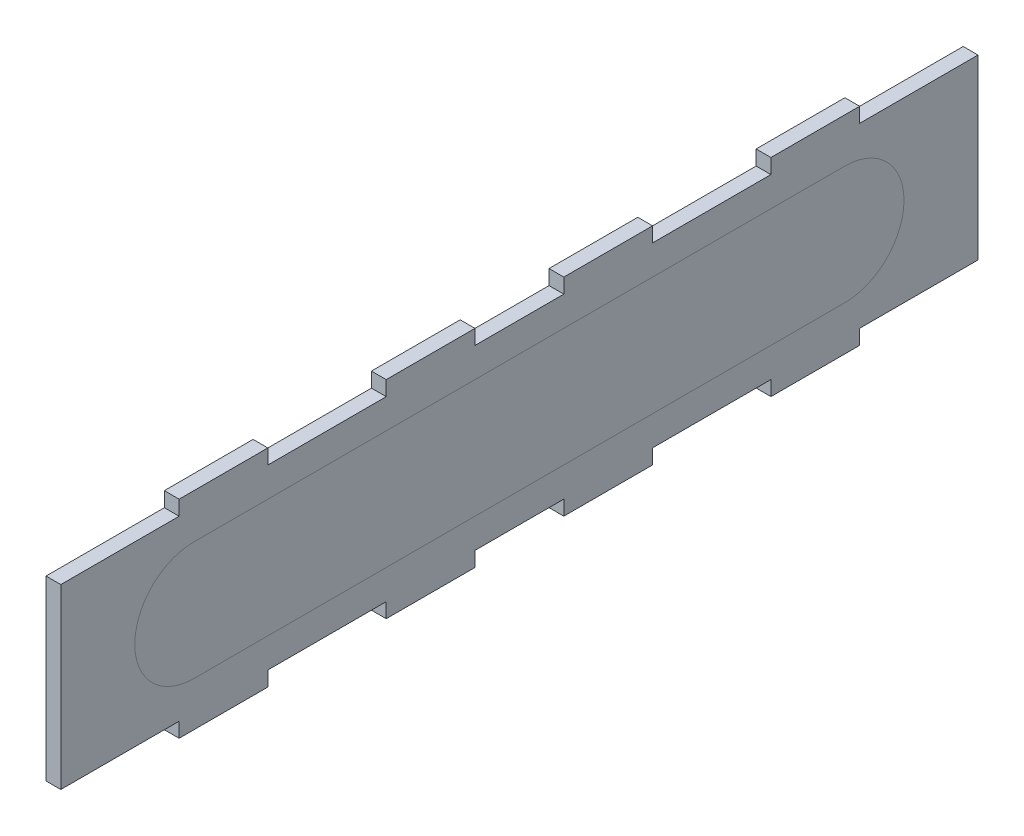
SolidWorks part; units mm, degrees
material "Maple"
ref_plane "Front Plane" through (0, 0, 0) normal (0, 0, 1) x (1, 0, 0)
ref_plane "Top Plane" through (0, 0, 0) normal (0, 1, 0) x (1, 0, 0)
ref_plane "Right Plane" through (0, 0, 0) normal (1, 0, 0) x (0, 0, -1)
sketch "Sketch1" plane through (0, 0, 0) normal (1, 0, 0) x (0, 0, -1)
  line L0 (-77.507, 17.5) -> (77.507, 17.5) construction
  line L1 (-77.507, -15) -> (77.507, -15) construction
  line L2 (-77.507, -15) -> (-77.507, 15) construction
  line L3 (-77.507, 15) -> (77.507, 15) construction
  line L4 (77.507, -15) -> (77.507, 15) construction
  line L5 (-77.507, -15) -> (77.507, 15) construction
  line L6 (-77.507, 15) -> (77.507, -15) construction
  line L7 (-77.507, -17.5) -> (77.507, -17.5) construction
  line L8 (-20.5112, 0) -> (21.2154, 0) construction
  line L9 (0, 9.427) -> (0, -9.8875) construction
  line L10 (-77.507, 15) -> (-77.507, -15)
  line L11 (-77.507, -15) -> (-57.507, -15)
  line L12 (-57.507, -15) -> (-57.507, -17.5)
  line L13 (-57.507, -17.5) -> (-42.507, -17.5)
  line L14 (-42.507, -17.5) -> (-42.507, -15)
  line L15 (-42.507, -15) -> (-22.507, -15)
  line L16 (-22.507, -15) -> (-22.507, -17.5)
  line L17 (-22.507, -17.5) -> (-7.507, -17.5)
  line L18 (-7.507, -17.5) -> (-7.507, -15)
  line L19 (-7.507, -15) -> (7.507, -15)
  line L20 (-7.507, 15) -> (7.507, 15)
  line L21 (-7.507, 17.5) -> (-7.507, 15)
  line L22 (-22.507, 17.5) -> (-7.507, 17.5)
  line L23 (-22.507, 15) -> (-22.507, 17.5)
  line L24 (-42.507, 15) -> (-22.507, 15)
  line L25 (-42.507, 17.5) -> (-42.507, 15)
  line L26 (-57.507, 17.5) -> (-42.507, 17.5)
  line L27 (-57.507, 15) -> (-57.507, 17.5)
  line L28 (-77.507, 15) -> (-57.507, 15)
  line L29 (7.507, -17.5) -> (7.507, -15)
  line L30 (22.507, -17.5) -> (7.507, -17.5)
  line L31 (22.507, -15) -> (22.507, -17.5)
  line L32 (42.507, -15) -> (22.507, -15)
  line L33 (42.507, -17.5) -> (42.507, -15)
  line L34 (57.507, -17.5) -> (42.507, -17.5)
  line L35 (57.507, -15) -> (57.507, -17.5)
  line L36 (77.507, -15) -> (57.507, -15)
  line L37 (77.507, 15) -> (77.507, -15)
  line L38 (77.507, 15) -> (57.507, 15)
  line L39 (57.507, 15) -> (57.507, 17.5)
  line L40 (57.507, 17.5) -> (42.507, 17.5)
  line L41 (42.507, 17.5) -> (42.507, 15)
  line L42 (42.507, 15) -> (22.507, 15)
  line L43 (22.507, 15) -> (22.507, 17.5)
  line L44 (22.507, 17.5) -> (7.507, 17.5)
  line L45 (7.507, 17.5) -> (7.507, 15)
  line L46 (-55, 0) -> (55, 0) construction
  line L47 (-55, 10) -> (55, 10)
  line L48 (-55, -10) -> (55, -10)
  arc A0 (-55, 10) -> (-55, -10) centre (-55, 0) ccw
  arc A1 (55, -10) -> (55, 10) centre (55, 0) ccw
  point P0 (0, 0)
  point P33 (-77.507, 0)
  point P34 (0, -15)
  point P49 (0, 15)
  point P51 (0, 0)
  dimension "D8" = 10
  dimension "D3" = 155.014
  dimension "D4" = 30
  dimension "D5" = 15
  dimension "D6" = 20
  dimension "D7" = 110
  dimension "D1" = 2.5
  dimension "D2" = 2.5
extrude "Boss-Extrude1" add sketch "Sketch1" along normal mid plane 2.5
extrude "Boss-Extrude2" add sketch "Sketch1<2>" along normal mid plane 2.5 separate body contours L48 A1 L47 A0 region at (0, 0, 0)
sketch "Sketch1<2>" plane through (0, 0, 0) normal (1, 0, 0) x (0, 0, -1) same geometry as "Sketch1"
